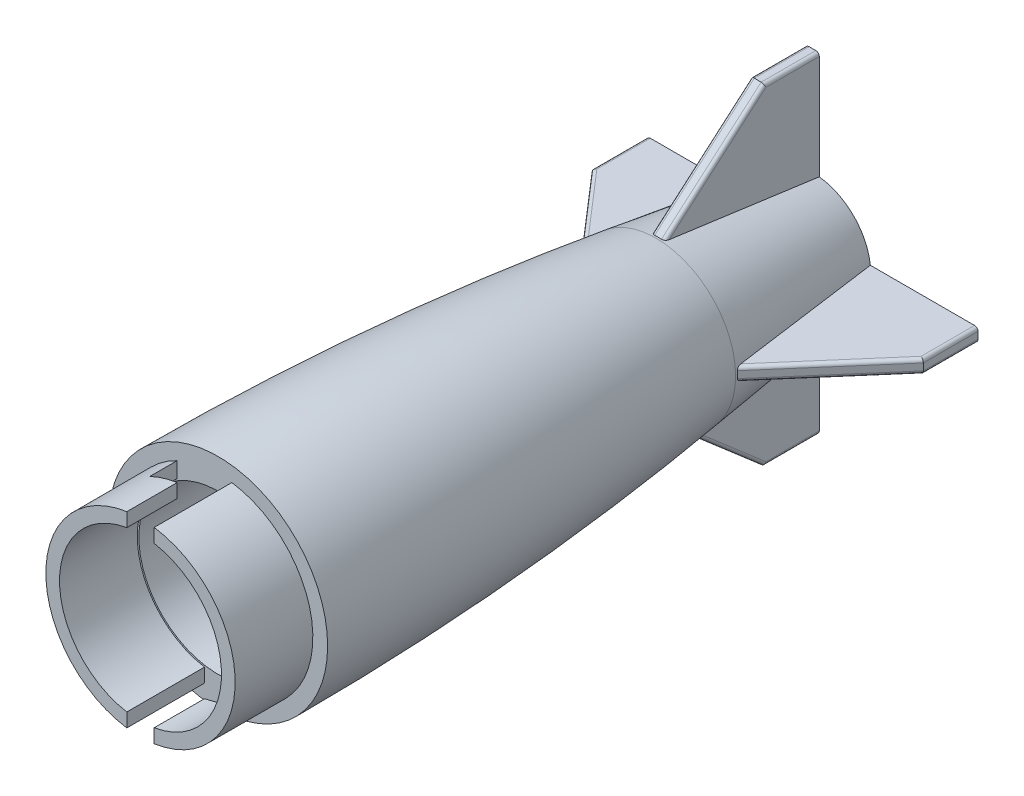
SolidWorks part; units mm, degrees
ref_plane "Front Plane" through (0, 0, 0) normal (0, 0, 1) x (1, 0, 0)
ref_plane "Top Plane" through (0, 0, 0) normal (0, 1, 0) x (1, 0, 0)
ref_plane "Right Plane" through (0, 0, 0) normal (1, 0, 0) x (0, 0, -1)
sketch "Sketch3" plane through (0, 0, 0) normal (1, 0, 0) x (0, 0, -1)
  line L0 (0, 0) -> (152.4, 0)
  line L1 (152.4, 0) -> (152.4, 3.175)
  line L2 (47.625, 0) -> (120.65, 0)
  line L3 (38.1, 12.7) -> (57.15, 12.7)
  line L5 (107.95, 9.2466) -> (152.4, 3.175)
  line L6 (0, 0) -> (0, 0.7937)
  line L7 (120.65, 0) -> (120.65, 3.683)
  line L8 (120.65, 3.683) -> (115.57, 3.683)
  line L9 (47.625, 9.2075) -> (98.425, 9.2075)
  line L10 (120.65, 2.8892) -> (122.2375, 2.8892)
  line L11 (122.2375, 2.8892) -> (126.1138, 6.7655)
  line L12 (57.15, 12.7) -> (57.15, 0)
  line L13 (38.4175, 0) -> (38.4175, 7.7847) construction
  arc A1 (57.15, 12.7) -> (107.95, 9.2466) centre (57.15, -362.6607) cw
  arc A2 (0, 0.7937) -> (38.1, 12.7) centre (38.1, -54.2131) cw
  circle A3 centre (47.625, 0) radius 9.2075
  arc A4 (98.425, 9.2075) -> (113.1409, 4.4657) centre (98.425, -15.9984) cw
  arc A5 (113.1409, 4.4657) -> (115.57, 3.683) centre (115.57, 7.8436) ccw
  spline S0 degree 3 poles (47.625, 9.2075) (44.4515, 9.2075) (39.1653, 8.9426) (38.4175, 4.2052) (38.4175, 0) knots 0 0 0 0 0.466662 1 1 1 1
  point P24 (113.8155, 4.2808)
  dimension "D1" = 12.7
  dimension "D5" = 44.45
  dimension "D6" = 0.7937
  dimension "D8" = 73.025
  dimension "D9" = 18.415
  dimension "D2" = 38.1
  dimension "D3" = 3.175
  dimension "D4" = 19.05
  dimension "D7" = 152.4
  dimension "D10" = 3.683
  dimension "D11" = 5.08
  dimension "D12" = 31.75
  dimension "D13" = 1.5875
  dimension "D14" = 0.7937
  dimension "D15" = 135
  dimension "D16" = 50.8
revolve "Revolve2" add sketch "Sketch3" angle 360 about L0 region at (0, 10.9538, -57.8466)
sketch "Sketch5" plane through (0, 0, 0) normal (1, 0, 0) x (0, 0, -1)
  line L1 (119.7638, 19.2115) -> (126.1138, 19.2115)
  line L2 (119.7638, 19.2115) -> (107.95, 8.9926)
  line L3 (126.1138, 19.2115) -> (126.1138, 6.5115)
  line L5 (126.1138, 6.7655) -> (126.1138, -6.7655) construction
  line L8 (126.1138, 6.5115) -> (107.95, 8.9926)
  line L9 (107.95, 8.9926) -> (107.95, -9.2466) construction
  line L10 (107.95, 9.2466) -> (107.95, -9.2466) construction
  dimension "D1" = 12.7
  dimension "D2" = 6.35
  dimension "D3" = 0.254
  dimension "D4" = 0.254
extrude "Boss-Extrude2" add sketch "Sketch5" along normal mid plane 1.5875 contours L8 L3 L1 L2 region at (0, 12.5013, -119.5945)
fillet "Fillet2" radius 0.3969 4 edges at (0.7937, 19.2115, -122.9388) (-0.7937, 19.2115, -122.9388) (0.7937, 14.1969, -113.9666) (-0.7937, 14.1969, -113.9666)
pattern_circular "CirPattern5" count 4 over 360 about axis through (0, 0, -122.2375) along (0, 0, 1) of "Fillet2", "Boss-Extrude2"
sketch "Sketch6" plane through (0, 0, -57.15) normal (0, 0, 1) x (1, 0, 0)
  circle A0 centre (0, 0) radius 9.398
  circle A1 centre (0, 0) radius 10.9855
  dimension "D1" = 18.796
  dimension "D2" = 1.5875
extrude "Boss-Extrude3" add sketch "Sketch6" along normal blind 9.017
sketch "Sketch8" plane through (0, 0, 0) normal (0, 1, 0) x (1, 0, 0)
  line L0 (-10.9855, 48.133) -> (10.9855, 48.133) construction
  line L1 (1.5875, 39.116) -> (-1.5875, 39.116)
  line L2 (1.5875, 39.116) -> (1.5875, 57.15)
  line L3 (1.5875, 57.15) -> (-1.5875, 57.15)
  line L4 (-1.5875, 39.116) -> (-1.5875, 57.15)
  line L5 (1.5875, 39.116) -> (-1.5875, 57.15) construction
  line L6 (1.5875, 57.15) -> (-1.5875, 39.116) construction
  line L7 (-10.9855, 57.15) -> (10.9855, 57.15) construction
  line L9 (4.7625, 53.975) -> (-4.7625, 53.975)
  line L10 (4.7625, 53.975) -> (4.7625, 57.15)
  line L11 (4.7625, 57.15) -> (-4.7625, 57.15)
  line L12 (-4.7625, 53.975) -> (-4.7625, 57.15)
  line L13 (4.7625, 53.975) -> (-4.7625, 57.15) construction
  line L14 (4.7625, 57.15) -> (-4.7625, 53.975) construction
  point P0 (0, 48.133)
  point P9 (0, 55.5625)
  dimension "D1" = 3.175
  dimension "D2" = 3.175
  dimension "D3" = 9.525
extrude "Cut-Extrude1" cut sketch "Sketch8" against normal through all contours L2 L9 L4 L1 | L9 L2 L3 L4 | L10 L11 L2 L9 region at (0, 0, -46.5455) region at (0, 0, -55.5625) region at (3.175, 0, -55.5625)
extrude "Cut-Extrude2" cut sketch "Sketch8<3>" along normal up to surface (10.8702 mm away) contours L2 L9 L4 L1 | L9 L2 L3 L4 | L12 L9 L4 L11 region at (0, 0, -46.5455) region at (0, 0, -55.5625) region at (-3.175, 0, -55.5625) up to face at (1.0524, -3.3834, -53.086)
sketch "Sketch8<3>" plane through (0, 0, 0) normal (0, 1, 0) x (1, 0, 0) same geometry as "Sketch8"
